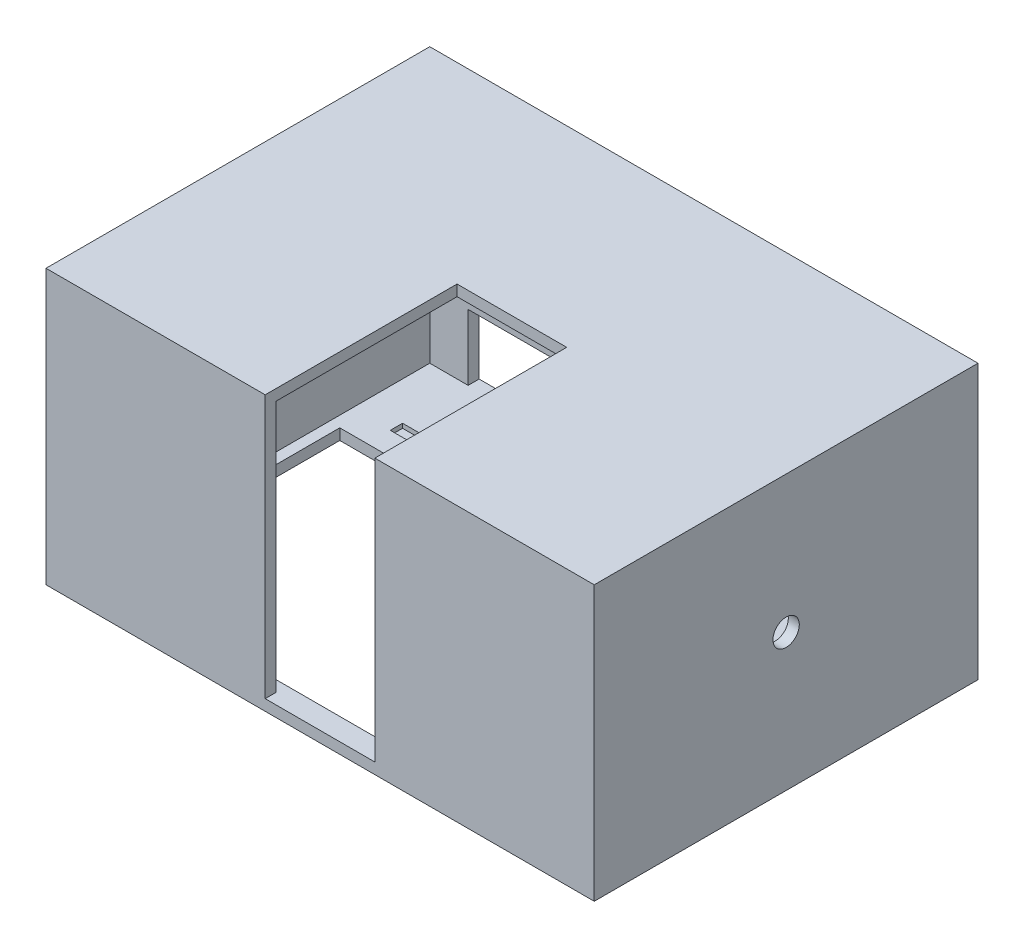
SolidWorks part; units mm, degrees
ref_plane "Front Plane" through (0, 0, 0) normal (0, 0, 1) x (1, 0, 0)
ref_plane "Top Plane" through (0, 0, 0) normal (0, 1, 0) x (1, 0, 0)
ref_plane "Right Plane" through (0, 0, 0) normal (1, 0, 0) x (0, 0, -1)
sketch "Sketch1" plane through (0, 0, 0) normal (0, 1, 0) x (1, 0, 0)
  line L0 (250, 0) -> (0, 0) construction
  line L1 (0, 0) -> (-250, 0) construction
  line L2 (-125, -87.5) -> (125, -87.5)
  line L3 (-125, -87.5) -> (-125, 87.5)
  line L4 (125, -87.5) -> (125, 87.5)
  line L5 (-125, 87.5) -> (125, 87.5)
  line L6 (-125, -87.5) -> (125, 87.5) construction
  line L7 (125, -87.5) -> (-125, 87.5) construction
  dimension "D1" = 175
  dimension "D2" = 250
extrude "Boss-Extrude1" add sketch "Sketch1" against normal blind 125
sketch "Sketch2" plane through (0, -125, 0) normal (0, -1, 0) x (1, 0, 0)
  line L0 (-125, 87.5) -> (125, 87.5) construction
  line L1 (-120, -82.5) -> (120, -82.5)
  line L2 (-120, -82.5) -> (-120, 82.5)
  line L3 (-120, 82.5) -> (120, 82.5)
  line L4 (120, -82.5) -> (120, 82.5)
  line L5 (-120, -82.5) -> (120, 82.5) construction
  line L6 (-120, 82.5) -> (120, -82.5) construction
  line L7 (125, 87.5) -> (125, -87.5) construction
  point P0 (0, 0)
  dimension "D1" = 5
  dimension "D2" = 5
extrude "Cut-Extrude1" cut sketch "Sketch2" against normal offset from surface (120 mm away) 5 up to face at (0, 0, 0)
sketch "Sketch3" plane through (0, 0, 0) normal (0, 1, 0) x (1, 0, 0)
  line L0 (-125, 0) -> (125, 0) construction
  line L1 (-125, 87.5) -> (-125, -87.5) construction
  line L2 (125, -87.5) -> (125, 87.5) construction
  line L3 (0, 87.5) -> (0, -120.2082) construction
  line L4 (-20.05, -82.5) -> (20.05, -82.5)
  line L5 (-20.05, -82.5) -> (-20.05, 82.5)
  line L6 (-20.05, 82.5) -> (20.05, 82.5)
  line L7 (20.05, -82.5) -> (20.05, 82.5)
  line L8 (-20.05, -82.5) -> (20.05, 82.5) construction
  line L9 (-20.05, 82.5) -> (20.05, -82.5) construction
  line L10 (125, 87.5) -> (-125, 87.5) construction
  point P6 (0, 0)
  dimension "D1" = 40.1
  dimension "D2" = 5
extrude "Cut-Extrude2" cut sketch "Sketch3" against normal through all
sketch "Sketch4" plane through (-125, 0, 0) normal (-1, 0, 0) x (0, 0, 1)
  line L0 (0, 0) -> (0, -125) construction
  line L1 (-87.5, -125) -> (87.5, -125) construction
  circle A0 centre (0, -62.5) radius 6
  point P7 (0, -62.5)
  point P8 (0, -62.5)
  point P10 (0, -62.5)
  dimension "D1" = 62.5
  dimension "D2" = 12
sketch "Sketch6" plane through (0, -125, 0) normal (0, -1, 0) x (1, 0, 0)
  line L1 (-125, 87.5) -> (125, 87.5)
  line L2 (-125, 87.5) -> (-125, -87.5)
  line L3 (-125, -87.5) -> (125, -87.5)
  line L4 (125, 87.5) -> (125, -87.5)
extrude "Boss-Extrude2" add sketch "Sketch6" against normal blind 5
sketch "Sketch7" plane through (0, 0, -87.5) normal (0, 0, -1) x (-1, 0, 0)
  line L0 (0, 0) -> (0, -125) construction
  line L1 (-125, -125) -> (125, -125) construction
  line L3 (-102.5, -120) -> (102.5, -120)
  line L4 (-102.5, -120) -> (-102.5, -90)
  line L5 (-102.5, -90) -> (102.5, -90)
  line L6 (102.5, -120) -> (102.5, -90)
  line L7 (-102.5, -120) -> (102.5, -90) construction
  line L8 (-102.5, -90) -> (102.5, -120) construction
  point P5 (0, -105)
  dimension "D1" = 205
  dimension "D2" = 30
  dimension "D3" = 5
extrude "Piano Plug" cut sketch "Sketch7" against normal up to surface (5 mm away) up to face at (0, -32.5, -82.5)
sketch "Sketch8" plane through (0, 0, 0) normal (0, 1, 0) x (1, 0, 0)
  line L0 (125, 87.5) -> (-125, 87.5) construction
  line L1 (-25.05, 87.5) -> (24.95, 87.5)
  line L2 (-25.05, 87.5) -> (-25.05, -92.5)
  line L3 (-25.05, -92.5) -> (24.95, -92.5)
  line L4 (24.95, 87.5) -> (24.95, -92.5)
  line L5 (-20.05, 82.5) -> (-20.05, -82.5) construction
  dimension "D1" = 50
  dimension "D2" = 5
  dimension "D3" = 180
extrude "Arm Hole" cut sketch "Sketch8" against normal up to surface (120 mm away) up to face at (0, -120, -42.5)
sketch "Sketch9" plane through (-25.05, 0, 0) normal (1, 0, 0) x (0, 0, -1)
  line L0 (87.5, 0) -> (87.5, -90)
  line L13 (0, 0) -> (0, -5)
  line L14 (87.5, 0) -> (-87.5, 0) construction
  line L15 (-82.5, -5) -> (82.5, -5) construction
  line L16 (0, -5) -> (82.5, -5)
  line L17 (82.5, -5) -> (82.5, -90)
  line L18 (82.5, -90) -> (87.5, -90)
  line L19 (0, 0) -> (87.5, 0)
extrude "Boss-Extrude8" add sketch "Sketch9" along normal through all
extrude "Main Shaft Hole" cut sketch "Sketch4" against normal through all
sketch "Sketch10" plane through (-125, 0, 0) normal (-1, 0, 0) x (0, 0, 1)
  circle A0 centre (50.8, -62.5) radius 20
  dimension "D2" = 40
  dimension "D1" = 50.8
extrude "Cut-Extrude8" cut sketch "Sketch10" against normal blind 33 and the other way blind 16
sketch "Sketch11" plane through (0, -125, 0) normal (0, -1, 0) x (-1, 0, 0)
  line L0 (125, -87.5) -> (-125, -87.5) construction
  line L1 (115, -77.5) -> (-115, -77.5)
  line L2 (115, -77.5) -> (115, 77.5)
  line L3 (115, 77.5) -> (-115, 77.5)
  line L4 (-115, -77.5) -> (-115, 77.5)
  line L5 (125, 87.5) -> (125, -87.5) construction
  line L6 (-125, 87.5) -> (125, 87.5) construction
  line L7 (-125, -87.5) -> (-125, 87.5) construction
  dimension "D1" = 10
  dimension "D2" = 10
  dimension "D3" = 10
  dimension "D4" = 10
extrude "Bottom Open" cut sketch "Sketch11" against normal blind 21 and the other way blind 28
sketch "Sketch12" plane through (-115, 0, 0) normal (1, 0, 0) x (0, 0, -1)
  line L0 (77.5, -125) -> (-77.5, -125) construction
  line L1 (77.5, -120) -> (36.4665, -120)
  line L2 (77.5, -120) -> (77.5, -125)
  line L3 (77.5, -125) -> (36.4665, -125)
  line L4 (36.4665, -120) -> (36.4665, -125)
extrude "Boss-Extrude4" add sketch "Sketch12" along normal blind 233
sketch "Sketch13" plane through (0, 0, 82.5) normal (0, 0, -1) x (-1, 0, 0)
  line L0 (120, -120) -> (25.05, -120) construction
  line L1 (101.5, -120) -> (94, -120)
  line L2 (101.5, -120) -> (101.5, -40)
  line L3 (101.5, -40) -> (94, -40)
  line L4 (94, -120) -> (94, -40)
  line L5 (120, -5) -> (120, -120) construction
  dimension "D1" = 7.5
  dimension "D2" = 18.5
  dimension "D3" = 80
extrude "Boss-Extrude5" add sketch "Sketch13" along normal blind 49
sketch "Sketch14" plane through (-115, 0, 0) normal (1, 0, 0) x (0, 0, -1)
  line L0 (-77.5, -125) -> (36.4665, -125) construction
  line L1 (-77.5, -120) -> (-33.3868, -120)
  line L2 (-77.5, -120) -> (-77.5, -125)
  line L3 (-77.5, -125) -> (-33.3868, -125)
  line L4 (-33.3868, -120) -> (-33.3868, -125)
extrude "Boss-Extrude6" add sketch "Sketch14" along normal blind 21
fillet "Fillet2" radius 5 1 edges at (-97.75, -120, 33.5)
sketch "Sketch16" plane through (0, 0, 0) normal (1, 0, 0) x (0, 0, -1)
  line L1 (-60.6684, -48.7422) -> (-40.6684, -48.7422)
  line L2 (-60.6684, -48.7422) -> (-60.6684, -102.7422)
  line L3 (-60.6684, -102.7422) -> (-40.6684, -102.7422)
  line L4 (-40.6684, -48.7422) -> (-40.6684, -102.7422)
  line L5 (-60.6684, -102.7422) -> (-40.6684, -102.7422)
  line L6 (-60.6684, -102.7422) -> (-60.6684, -96.7422)
  line L7 (-60.6684, -96.7422) -> (-40.6684, -96.7422)
  line L8 (-40.6684, -102.7422) -> (-40.6684, -96.7422)
  line L9 (-60.6684, -48.7422) -> (-40.6684, -48.7422)
  line L10 (-60.6684, -48.7422) -> (-60.6684, -54.7422)
  line L11 (-60.6684, -54.7422) -> (-40.6684, -54.7422)
  line L12 (-40.6684, -48.7422) -> (-40.6684, -54.7422)
  circle A0 centre (-55.7934, -51.7422) radius 2.5
  circle A1 centre (-45.5434, -51.7422) radius 2.5
  circle A2 centre (-55.7934, -99.7422) radius 2.5
  circle A3 centre (-45.5434, -99.7422) radius 2.5
  dimension "D3" = 5
  dimension "D6" = 5
  dimension "D8" = 5
  dimension "D11" = 5
  dimension "D1" = 20
  dimension "D2" = 54
  dimension "D4" = 3
  dimension "D5" = 4.875
  dimension "D7" = 4.875
  dimension "D9" = 3
  dimension "D10" = 4.875
  dimension "D12" = 6
  dimension "D13" = 6
extrude "Servo Plug Hole" cut sketch "Sketch16" against normal blind 106 contours A1 | A0 | L11 L2 L7 L4 | A3 | A2 region at (0, -75.7422, 50.6684) region at (0, -51.7422, 55.7934) region at (0, -51.7422, 45.5434) region at (0, -99.7422, 55.7934) region at (0, -99.7422, 45.5434)
sketch "Sketch17" plane through (-101.5, 0, 0) normal (-1, 0, 0) x (0, 0, 1)
  line L0 (82.5, -120) -> (82.5, -40) construction
  line L1 (33.3868, -120) -> (82.5, -120)
  line L2 (33.3868, -120) -> (33.3868, -107.8359)
  line L3 (33.3868, -107.8359) -> (82.5, -107.8359)
  line L4 (82.5, -120) -> (82.5, -107.8359)
extrude "Boss-Extrude7" add sketch "Sketch17" along normal blind 23
sketch "Sketch19" plane through (0, -120, 0) normal (0, 1, 0) x (1, 0, 0)
  line L0 (-120, 52.6) -> (120, 52.6) construction
  line L1 (-120, 82.5) -> (-120, -82.5) construction
  line L2 (120, -82.5) -> (120, 82.5) construction
  line L3 (102.5, 87.5) -> (102.5, 36.4665) construction
  line L4 (-102.5, 87.5) -> (-102.5, 36.4665) construction
  line L5 (115, 36.4665) -> (-115, 36.4665) construction
  line L6 (0, 87.5) -> (0, 36.4665) construction
  line L7 (102.5, 87.5) -> (-102.5, 87.5) construction
  line L8 (-120, 47) -> (120, 47) construction
  line L9 (-120, 82.5) -> (-120, -33.3868) construction
  line L10 (120, -82.5) -> (120, 82.5) construction
  line L12 (102.5, 47) -> (92.4, 47)
  line L13 (102.5, 47) -> (102.5, 52.6)
  line L14 (102.5, 52.6) -> (92.4, 52.6)
  line L15 (92.4, 47) -> (92.4, 52.6)
  line L16 (-102.5, 52.6) -> (-92.4, 52.6)
  line L17 (-102.5, 52.6) -> (-102.5, 47)
  line L18 (-102.5, 47) -> (-92.4, 47)
  line L19 (-92.4, 52.6) -> (-92.4, 47)
  line L20 (-5.05, 47) -> (5.05, 47)
  line L21 (-5.05, 47) -> (-5.05, 52.6)
  line L22 (-5.05, 52.6) -> (5.05, 52.6)
  line L23 (5.05, 47) -> (5.05, 52.6)
  line L24 (-5.05, 47) -> (5.05, 52.6) construction
  line L25 (-5.05, 52.6) -> (5.05, 47) construction
  point P32 (0, 49.8)
  dimension "D1" = 40.5
  dimension "D2" = 34.9
  dimension "D3" = 10.1
extrude "Cut-Extrude9" cut sketch "Sketch19" against normal blind 2
sketch "Sketch21" plane through (0, 0, -87.5) normal (0, 0, -1) x (-1, 0, 0)
  line L0 (-102.5, -120) -> (-102.5, -125) construction
  line L1 (-115, -125) -> (115, -125) construction
  line L2 (102.5, -120) -> (102.5, -125) construction
  line L3 (-125, -125) -> (125, -125) construction
  line L4 (0, -120) -> (0, -125) construction
  line L5 (-102.5, -120) -> (102.5, -120) construction
  line L6 (-102.5, -124.55) -> (102.5, -124.55) construction
  line L8 (-102.5, -124.55) -> (-92.4, -124.55)
  line L9 (-102.5, -124.55) -> (-102.5, -123.45)
  line L10 (-102.5, -123.45) -> (-92.4, -123.45)
  line L11 (-92.4, -124.55) -> (-92.4, -123.45)
  line L12 (102.5, -124.55) -> (92.4, -124.55)
  line L13 (102.5, -124.55) -> (102.5, -123.45)
  line L14 (102.5, -123.45) -> (92.4, -123.45)
  line L15 (92.4, -124.55) -> (92.4, -123.45)
  line L16 (-5.05, -123.45) -> (5.05, -123.45)
  line L17 (-5.05, -123.45) -> (-5.05, -124.55)
  line L18 (-5.05, -124.55) -> (5.05, -124.55)
  line L19 (5.05, -123.45) -> (5.05, -124.55)
  line L20 (-5.05, -123.45) -> (5.05, -124.55) construction
  line L21 (-5.05, -124.55) -> (5.05, -123.45) construction
  point P22 (0, -124)
  dimension "D1" = 0.45
  dimension "D2" = 1.1
  dimension "D3" = 10.1
extrude "Cut-Extrude10" cut sketch "Sketch21" against normal blind 10
